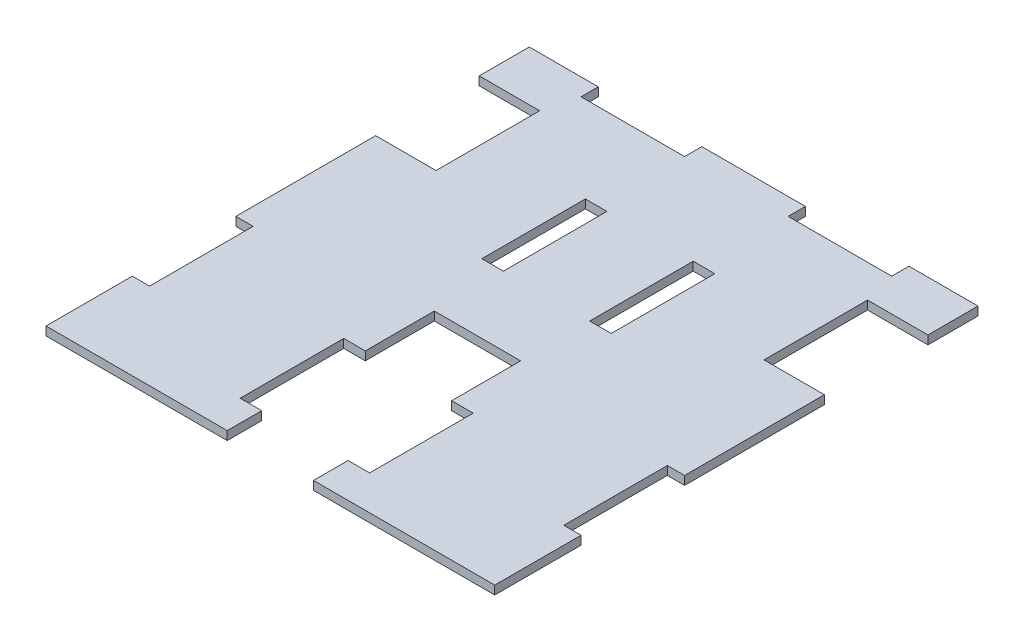
SolidWorks part; units mm, degrees
material "7050-T73510"
ref_plane "Front Plane" through (0, 0, 0) normal (0, 0, 1) x (1, 0, 0)
ref_plane "Top Plane" through (0, 0, 0) normal (0, 1, 0) x (1, 0, 0)
ref_plane "Right Plane" through (0, 0, 0) normal (1, 0, 0) x (0, 0, -1)
sketch "Sketch1" plane through (0, 0, 0) normal (0, 1, 0) x (1, 0, 0)
  line L1 (-165.1, -177.8) -> (165.1, -177.8)
  line L2 (-165.1, -177.8) -> (-165.1, 177.8)
  line L3 (-165.1, 177.8) -> (165.1, 177.8)
  line L4 (165.1, -177.8) -> (165.1, 177.8)
  line L5 (-165.1, -177.8) -> (165.1, 177.8) construction
  line L6 (-165.1, 177.8) -> (165.1, -177.8) construction
  point P0 (0, 0)
  dimension "D1" = 355.6
  dimension "D2" = 330.2
extrude "Boss-Extrude1" add sketch "Sketch1" along normal blind 6.35
sketch "Sketch2" plane through (0, 6.35, 0) normal (0, 1, 0) x (1, 0, 0)
  line L0 (-165.1, -177.8) -> (165.1, -177.8) construction
  line L1 (-31.75, -25.4) -> (31.75, -25.4)
  line L2 (-31.75, -25.4) -> (-31.75, -177.8)
  line L3 (-31.75, -177.8) -> (31.75, -177.8)
  line L4 (31.75, -25.4) -> (31.75, -177.8)
  line L5 (-31.75, -25.4) -> (31.75, -177.8) construction
  line L6 (-31.75, -177.8) -> (31.75, -25.4) construction
  point P0 (0, -101.6)
  dimension "D1" = 152.4
  dimension "D2" = 63.5
extrude "Cut-Extrude1" cut sketch "Sketch2" against normal through all
sketch "Sketch3" plane through (0, 6.35, 0) normal (0, 1, 0) x (1, 0, 0)
  line L1 (120.65, 140.97) -> (165.1, 140.97)
  line L2 (120.65, 140.97) -> (120.65, 64.77)
  line L3 (120.65, 64.77) -> (165.1, 64.77)
  line L4 (165.1, 140.97) -> (165.1, 64.77)
  line L6 (0, -3.4925) -> (0, 3.4925) construction
  line L7 (-120.65, 64.77) -> (-165.1, 64.77)
  line L8 (-165.1, 140.97) -> (-165.1, 64.77)
  line L9 (-120.65, 140.97) -> (-165.1, 140.97)
  line L10 (-120.65, 140.97) -> (-120.65, 64.77)
  line L12 (165.1, -177.8) -> (165.1, 177.8) construction
  line L14 (165.1, 177.8) -> (-165.1, 177.8) construction
  dimension "D1" = 76.2
  dimension "D2" = 44.45
  dimension "D3" = 36.83
extrude "Cut-Extrude2" cut sketch "Sketch3" against normal through all
sketch "Sketch4" plane through (0, 6.35, 0) normal (0, 1, 0) x (1, 0, 0)
  line L0 (-165.1, 177.8) -> (-165.1, 140.97) construction
  line L1 (-165.1, 140.97) -> (-152.4, 140.97)
  line L2 (-165.1, 140.97) -> (-165.1, 64.77)
  line L3 (-165.1, 64.77) -> (-152.4, 64.77)
  line L4 (-152.4, 140.97) -> (-152.4, 64.77)
  line L5 (0, -3.4925) -> (0, 3.4925) construction
  line L6 (-165.1, -114.3) -> (-152.4, -114.3)
  line L7 (-165.1, -114.3) -> (-165.1, -38.1)
  line L8 (-165.1, -38.1) -> (-152.4, -38.1)
  line L9 (-152.4, -114.3) -> (-152.4, -38.1)
  line L10 (165.1, 64.77) -> (152.4, 64.77)
  line L11 (152.4, 140.97) -> (152.4, 64.77)
  line L12 (165.1, 140.97) -> (152.4, 140.97)
  line L13 (165.1, 140.97) -> (165.1, 64.77)
  line L14 (165.1, -38.1) -> (152.4, -38.1)
  line L15 (152.4, -114.3) -> (152.4, -38.1)
  line L16 (165.1, -114.3) -> (152.4, -114.3)
  line L17 (165.1, -114.3) -> (165.1, -38.1)
  line L18 (165.1, 177.8) -> (-165.1, 177.8) construction
  line L19 (114.3, 165.1) -> (38.1, 165.1)
  line L20 (-114.3, 177.8) -> (-38.1, 177.8)
  line L21 (-114.3, 177.8) -> (-114.3, 165.1)
  line L22 (-114.3, 165.1) -> (-38.1, 165.1)
  line L23 (-38.1, 177.8) -> (-38.1, 165.1)
  line L24 (38.1, 177.8) -> (38.1, 165.1)
  line L25 (114.3, 177.8) -> (38.1, 177.8)
  line L26 (114.3, 177.8) -> (114.3, 165.1)
  line L27 (-31.75, -25.4) -> (-31.75, -177.8) construction
  line L28 (-31.75, -152.4) -> (-47.625, -152.4)
  line L29 (-31.75, -152.4) -> (-31.75, -76.2)
  line L30 (-31.75, -76.2) -> (-47.625, -76.2)
  line L31 (-47.625, -152.4) -> (-47.625, -76.2)
  line L32 (-165.1, -177.8) -> (-31.75, -177.8) construction
  line L33 (31.75, 101.6) -> (47.625, 101.6)
  line L34 (-31.75, 25.4) -> (-47.625, 25.4)
  line L35 (-31.75, 25.4) -> (-31.75, 101.6)
  line L36 (-31.75, 101.6) -> (-47.625, 101.6)
  line L37 (-47.625, 25.4) -> (-47.625, 101.6)
  line L38 (47.625, 25.4) -> (47.625, 101.6)
  line L39 (31.75, 25.4) -> (47.625, 25.4)
  line L40 (31.75, 25.4) -> (31.75, 101.6)
  line L41 (31.75, -76.2) -> (47.625, -76.2)
  line L42 (47.625, -152.4) -> (47.625, -76.2)
  line L43 (31.75, -152.4) -> (47.625, -152.4)
  line L44 (31.75, -152.4) -> (31.75, -76.2)
  dimension "D1" = 12.7
  dimension "D2" = 12.7
  dimension "D3" = 76.2
  dimension "D4" = 76.2
  dimension "D5" = 36.83
  dimension "D6" = 215.9
  dimension "D7" = 12.7
  dimension "D8" = 76.2
  dimension "D9" = 76.2
  dimension "D10" = 15.875
  dimension "D11" = 76.2
  dimension "D12" = 25.4
  dimension "D13" = 76.2
  dimension "D14" = 15.875
  dimension "D15" = 203.2
  dimension "D16" = 63.5
extrude "Cut-Extrude3" cut sketch "Sketch4" against normal through all
